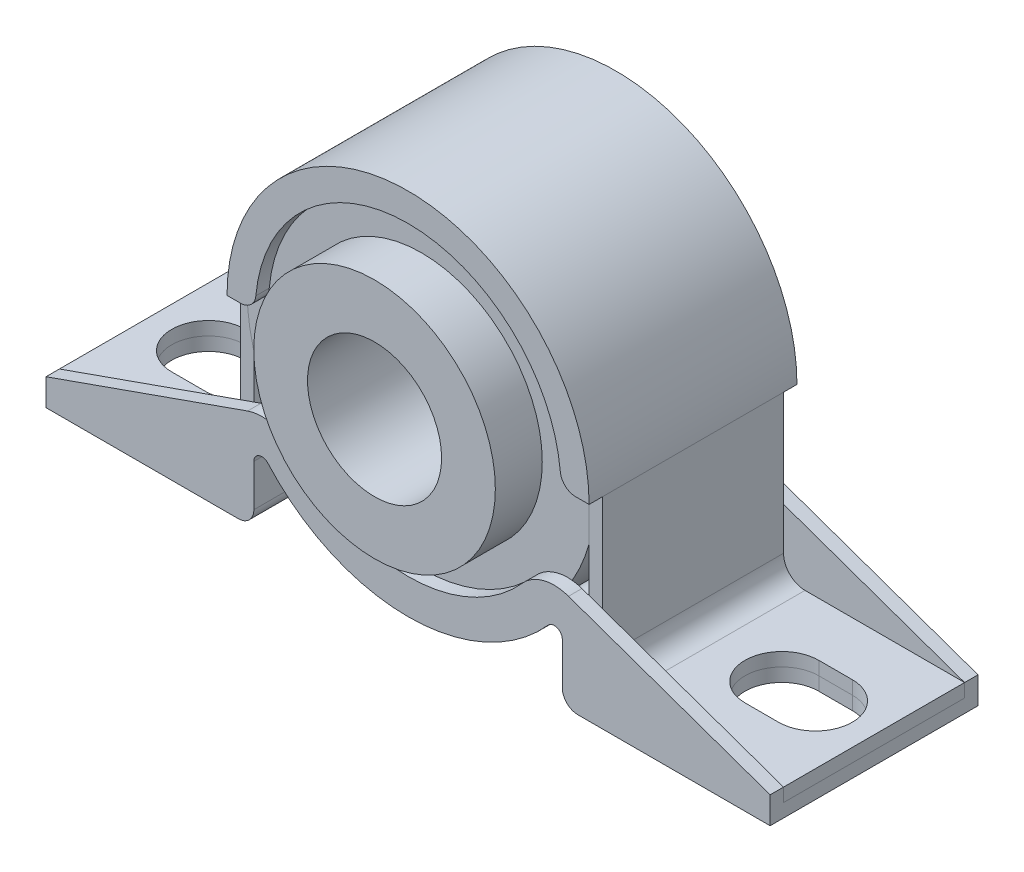
SolidWorks part; units mm, degrees
ref_plane "Front" through (0, 0, 0) normal (0, 0, 1) x (1, 0, 0)
ref_plane "Top" through (0, 0, 0) normal (0, 1, 0) x (1, 0, 0)
ref_plane "Right" through (0, 0, 0) normal (1, 0, 0) x (0, 0, -1)
sketch "Sketch1" plane through (0, 0, 0) normal (0, 0, 1) x (1, 0, 0)
  line L1 (-23.9712, -19.05) -> (-42.8625, -19.05) construction
  line L2 (-42.8625, -19.05) -> (-42.8625, -22.225) construction
  line L3 (-42.8625, -22.225) -> (42.8625, -22.225) construction
  line L6 (0, 0) -> (0, -22.225) construction
  line L9 (42.8625, -22.225) -> (42.8625, -19.05) construction
  line L10 (42.8625, -19.05) -> (23.9713, -19.05) construction
  line L12 (-21.4313, 0) -> (-21.4312, -16.51) construction
  line L13 (-42.8625, -20.6375) -> (-19.8438, -20.6375)
  line L14 (21.4313, 0) -> (21.4313, -16.51) construction
  line L15 (-19.8438, -20.6375) -> (-19.8438, -15.42)
  line L16 (19.8438, -15.42) -> (19.8438, -20.6375)
  line L17 (19.8438, -20.6375) -> (42.8625, -20.6375)
  circle A0 centre (0, 0) radius 7.9375 construction
  circle A1 centre (0, 0) radius 14.3002 construction
  arc A2 (21.4313, 0) -> (-21.4313, 0) centre (0, 0) ccw construction
  arc A5 (-21.4312, -16.51) -> (-23.9712, -19.05) centre (-23.9712, -16.51) cw construction
  arc A6 (21.4313, -16.51) -> (23.9713, -19.05) centre (23.9713, -16.51) ccw construction
  arc A7 (-19.8438, -15.42) -> (-15.4074, -13.7301) centre (-17.3038, -15.42) cw
  arc A8 (-15.4074, -13.7301) -> (15.4074, -13.7301) centre (0, 0) ccw
  arc A9 (15.4074, -13.7301) -> (19.8438, -15.42) centre (17.3038, -15.42) cw
  dimension "Shaft Dia" = 15.875
  dimension "K" = 28.6004
  dimension "D1" = 2.54
  dimension "w" = 43.6562
  dimension "h" = 22.225
  dimension "g" = 3.175
  dimension "a" = 85.725
  dimension "D2" = 1.5875
extrude "Extrude-Thin2" add sketch "Sketch1" along normal mid plane 24.6062 thin thin type one direction wall 1.5875
sketch "Sketch4" plane through (0, 0, 12.3031) normal (0, 0, 1) x (1, 0, 0)
  line L0 (-42.8625, -19.05) -> (-18.9938, -10.6294)
  line L1 (18.9938, -10.6294) -> (42.8625, -19.05)
  line L2 (-23.9712, -19.05) -> (-42.8625, -19.05) construction
  line L3 (42.8625, -19.05) -> (23.9713, -19.05) construction
  line L10 (20.0978, -22.225) -> (42.8625, -22.225)
  line L11 (42.8625, -22.225) -> (42.8625, -20.6375)
  line L12 (42.8625, -20.6375) -> (20.0978, -20.6375)
  line L13 (19.8438, -20.3835) -> (19.8438, -15.42)
  line L14 (-19.8438, -15.42) -> (-19.8438, -20.3835)
  line L15 (-20.0978, -20.6375) -> (-42.8625, -20.6375)
  line L16 (-42.8625, -20.6375) -> (-42.8625, -22.225)
  line L17 (-42.8625, -22.225) -> (-20.0978, -22.225)
  line L18 (-18.2563, -20.3835) -> (-18.2563, -15.42)
  line L19 (18.2563, -15.42) -> (18.2563, -20.3835)
  line L20 (20.0978, -22.225) -> (42.8625, -22.225)
  line L21 (42.8625, -22.225) -> (42.8625, -19.05)
  line L26 (-42.8625, -19.05) -> (-42.8625, -22.225)
  line L27 (-42.8625, -22.225) -> (-20.0978, -22.225)
  line L28 (-18.2563, -20.3835) -> (-18.2563, -15.42)
  line L29 (18.2563, -15.42) -> (18.2563, -20.3835)
  arc A0 (-13.5111, -12.0403) -> (-18.9938, -10.6294) centre (-17.3038, -15.42) ccw
  arc A1 (18.9938, -10.6294) -> (13.5111, -12.0403) centre (17.3038, -15.42) ccw
  arc A2 (-13.5111, -12.0403) -> (13.5111, -12.0403) centre (0, 0) ccw
  arc A10 (19.8438, -20.3835) -> (20.0978, -20.6375) centre (20.0978, -20.3835) ccw
  arc A11 (19.8438, -15.42) -> (15.4074, -13.7301) centre (17.3038, -15.42) ccw
  arc A12 (-15.4074, -13.7301) -> (15.4074, -13.7301) centre (0, 0) ccw
  arc A13 (-15.4074, -13.7301) -> (-19.8438, -15.42) centre (-17.3038, -15.42) ccw
  arc A14 (-20.0978, -20.6375) -> (-19.8438, -20.3835) centre (-20.0978, -20.3835) ccw
  arc A15 (-20.0978, -22.225) -> (-18.2563, -20.3835) centre (-20.0978, -20.3835) ccw
  arc A17 (-16.5926, -14.7863) -> (16.5926, -14.7863) centre (0, 0) ccw
  arc A19 (18.2563, -20.3835) -> (20.0978, -22.225) centre (20.0978, -20.3835) ccw
  arc A21 (-16.5926, -14.7863) -> (-18.2563, -15.42) centre (-17.3038, -15.42) ccw
  arc A22 (-16.5926, -14.7863) -> (-18.2563, -15.42) centre (-17.3038, -15.42) ccw
  arc A23 (18.2563, -15.42) -> (16.5926, -14.7863) centre (17.3038, -15.42) ccw
  arc A24 (18.2563, -15.42) -> (16.5926, -14.7863) centre (17.3038, -15.42) ccw
  arc A25 (-20.0978, -22.225) -> (-18.2563, -20.3835) centre (-20.0978, -20.3835) ccw
  arc A27 (-16.5926, -14.7863) -> (16.5926, -14.7863) centre (0, 0) ccw
  arc A29 (18.2563, -20.3835) -> (20.0978, -22.225) centre (20.0978, -20.3835) ccw
  dimension "D2" = 5.08
  dimension "D1" = 0
extrude "Extrude1" add sketch "Sketch4" against normal blind 1.5875
mirror "Mirror1" about plane through (0, 0, 0) normal (0, 0, 1) of "Extrude1"
sketch "Sketch5" plane through (0, 0, 0) normal (0, 0, 1) x (1, 0, 0)
  line L0 (42.8625, -19.05) -> (23.9713, -19.05) construction
  line L1 (21.4313, 0) -> (21.4313, -16.51) construction
  line L2 (-21.4313, 0) -> (-21.4312, -16.51) construction
  line L3 (-23.9712, -19.05) -> (-42.8625, -19.05) construction
  line L4 (42.8625, -19.05) -> (23.9713, -19.05)
  line L5 (21.4313, 0) -> (21.4313, -16.51)
  line L6 (-21.4313, 0) -> (-21.4312, -16.51)
  line L7 (-23.9712, -19.05) -> (-42.8625, -19.05)
  arc A0 (21.4313, -16.51) -> (23.9713, -19.05) centre (23.9713, -16.51) ccw construction
  arc A1 (21.4313, 0) -> (-21.4313, 0) centre (0, 0) ccw construction
  arc A2 (-23.9712, -19.05) -> (-21.4312, -16.51) centre (-23.9712, -16.51) ccw construction
  arc A3 (21.4313, -16.51) -> (23.9713, -19.05) centre (23.9713, -16.51) ccw
  arc A4 (21.4313, 0) -> (-21.4313, 0) centre (0, 0) ccw
  arc A5 (-23.9712, -19.05) -> (-21.4312, -16.51) centre (-23.9712, -16.51) ccw
extrude "Extrude-Thin3" add sketch "Sketch5" along normal up to surface (10.7156 mm away) and the other way up to surface (10.7156 mm away) separate body thin up to face at (0, -17.0875, 10.7156) other way up to face at (0, -17.0875, -10.7156) thin type one direction reverse wall 1.5875
sketch "Sketch6" plane through (0, 0, -10.7156) normal (0, 0, -1) x (-1, 0, 0)
  line L0 (-21.4313, 0) -> (21.4313, 0) construction
  line L1 (-19.8438, 0) -> (-21.4313, 0)
  line L2 (21.4313, 0) -> (19.8438, 0)
  arc A0 (21.4313, 0) -> (-21.4313, 0) centre (0, 0) ccw construction
  arc A1 (21.4313, 0) -> (-21.4313, 0) centre (0, 0) ccw
  arc A2 (-13.5111, -12.0403) -> (13.5111, -12.0403) centre (0, 0) ccw construction
  arc A3 (-13.5111, -12.0403) -> (18.0975, 0) centre (0, 0) ccw construction
  arc A4 (18.021, 1.6624) -> (-18.021, 1.6624) centre (0, 0) ccw
  arc A5 (19.8438, 0) -> (-19.8438, 0) centre (0, 0) ccw construction
  arc A6 (19.8438, 0) -> (-19.8438, 0) centre (0, 0) ccw construction
  arc A7 (-19.8438, 0) -> (-18.021, 1.6624) centre (-19.8438, 1.8305) ccw
  arc A8 (19.8438, 0) -> (18.021, 1.6624) centre (19.8438, 1.8305) cw
extrude "Extrude2" add sketch "Sketch6" along normal blind 1.5875
mirror "Mirror2" about plane through (0, 0, 0) normal (0, 0, 1) of "Extrude2"
sketch "Sketch7" plane through (0, 0, 0) normal (0, 0, 1) x (1, 0, 0)
  circle A0 centre (0, 0) radius 20.6375
  circle A1 centre (0, 0) radius 14.3002
  circle A2 centre (0, 0) radius 14.3002 construction
  arc A3 (-15.4074, -13.7301) -> (15.4074, -13.7301) centre (0, 0) ccw construction
extrude "Extrude3" add sketch "Sketch7" along normal up to surface (10.7156 mm away) and the other way up to surface (10.7156 mm away) separate body up to face at (0, -17.0875, 10.7156) other way up to face at (0, -17.0875, -10.7156)
ref_plane "Plane1" through (0, 0, 16.2719) normal (0, 0, -1) x (-1, 0, 0)
sketch "Sketch8" plane through (0, 0, 16.2719) normal (0, 0, 1) x (1, 0, 0)
  circle A0 centre (0, 0) radius 14.3002 construction
  circle A1 centre (0, 0) radius 7.9375 construction
  circle A2 centre (0, 0) radius 14.3002
  circle A3 centre (0, 0) radius 7.9375
extrude "Extrude4" add sketch "Sketch8" against normal blind 21.9989 separate body
sketch "Sketch3" plane through (0, 0, 0) normal (0, 1, 0) x (1, 0, 0)
  line L2 (-35.9172, 0) -> (-31.9484, 0) construction
  line L3 (-31.9484, 0) -> (0, 0) construction
  line L4 (0, 0) -> (31.9484, 0) construction
  line L5 (31.9484, 0) -> (35.9172, 0) construction
  line L6 (-35.9172, 4.3656) -> (-31.9484, 4.3656)
  line L7 (-35.9172, -4.3656) -> (-31.9484, -4.3656)
  line L8 (31.9484, -4.3656) -> (35.9172, -4.3656)
  line L9 (35.9172, 4.3656) -> (31.9484, 4.3656)
  arc A0 (-35.9172, 4.3656) -> (-35.9172, -4.3656) centre (-35.9172, 0) ccw
  arc A1 (-31.9484, 4.3656) -> (-31.9484, -4.3656) centre (-31.9484, 0) cw
  arc A2 (31.9484, 4.3656) -> (31.9484, -4.3656) centre (31.9484, 0) ccw
  arc A3 (35.9172, 4.3656) -> (35.9172, -4.3656) centre (35.9172, 0) cw
  point P13 (33.9328, -4.3656)
  point P14 (-33.9328, -4.3656)
  dimension "D1" = 67.8656
  dimension "Slot Width" = 8.7312
  dimension "Slot Length" = 12.7
extrude "Cut-Extrude1" cut sketch "Sketch3" against normal through all
sketch "Sketch9" plane through (0, 0, 0) normal (1, 0, 0) x (0, 0, -1)
  line L0 (-16.2719, 0) -> (5.7271, 0) construction
  line L1 (-16.2719, 14.3002) -> (-16.2719, -14.3002) construction
  line L2 (5.7271, -7.9375) -> (5.7271, 7.9375) construction
equation "\"D2@Sketch1\"=\"g@Sketch1\"/2"
equation "\"D5@Extrude-Thin2\"=\"g@Sketch1\"/2"
equation "\"D1@Extrude1\"=\"g@Sketch1\"/2"
equation "\"D5@Extrude-Thin3\" = \"g@Sketch1\"/2"
equation "\"D1@Extrude2\"=\"g@Sketch1\"/2"
